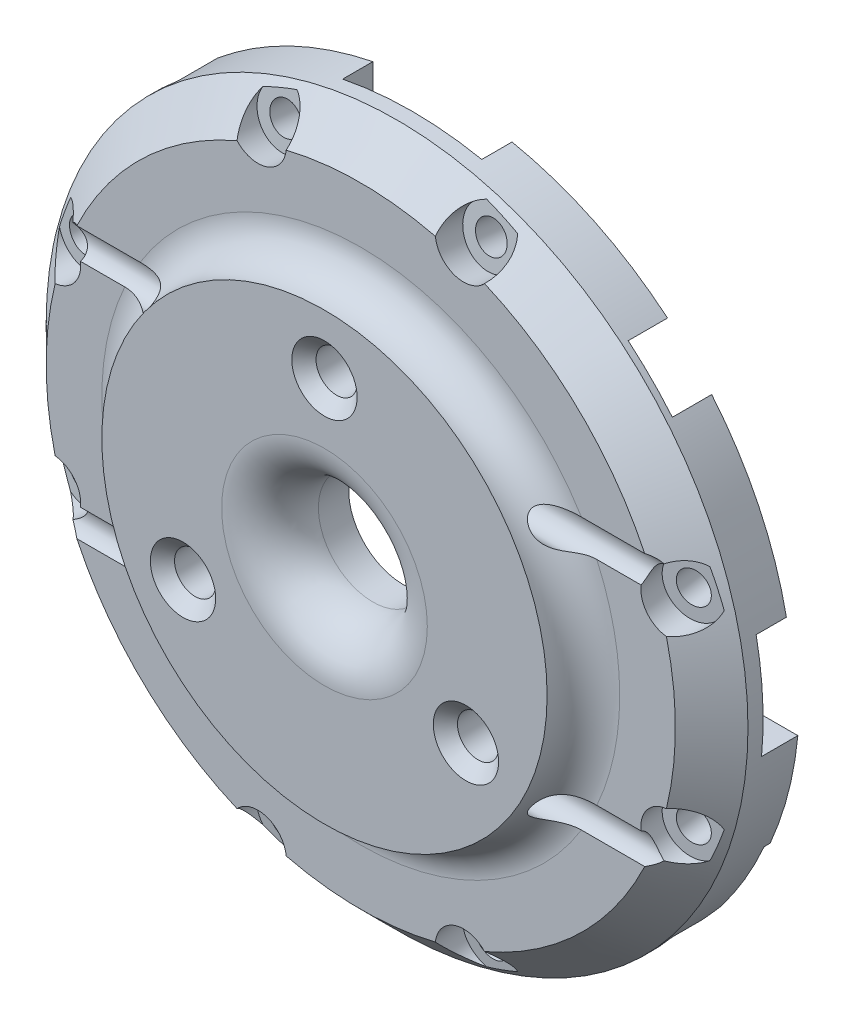
SolidWorks part; units mm, degrees
ref_plane "Front Plane" through (0, 0, 0) normal (0, 0, 1) x (1, 0, 0)
ref_plane "Top Plane" through (0, 0, 0) normal (0, 1, 0) x (1, 0, 0)
ref_plane "Right Plane" through (0, 0, 0) normal (1, 0, 0) x (0, 0, -1)
sketch "Sketch1" plane through (0, 0, 0) normal (0, 0, 1) x (1, 0, 0)
  circle A0 centre (0, 0) radius 29
  dimension "D1" = 58
extrude "Boss-Extrude1" add sketch "Sketch1" along normal blind 6.75
sketch "Sketch3" plane through (0, 0, 0) normal (0, 0, -1) x (-1, 0, 0)
  line L1 (-22.25, -22.25) -> (22.25, -22.25)
  line L2 (-22.25, -22.25) -> (-22.25, 22.25)
  line L3 (-22.25, 22.25) -> (22.25, 22.25)
  line L4 (22.25, -22.25) -> (22.25, 22.25)
  line L5 (-22.25, -22.25) -> (22.25, 22.25) construction
  line L6 (-22.25, 22.25) -> (22.25, -22.25) construction
  point P0 (0, 0)
  dimension "D1" = 44.5
extrude "Cut-Extrude1" cut sketch "Sketch3" against normal blind 3.25
sketch "Sketch4" plane through (0, 0, 6.75) normal (0, 0, 1) x (1, 0, 0)
  circle A0 centre (0, 0) radius 18.4
  dimension "D1" = 36.8
extrude "Boss-Extrude2" add sketch "Sketch4" along normal blind 3
fillet "Fillet1" radius 3 1 edges at (18.4, 0, 6.75)
sketch "Sketch5" plane through (0, 0, 9.75) normal (0, 0, 1) x (1, 0, 0)
  line L0 (-11.6913, -6.75) -> (0, 13.5) construction
  line L1 (0, 13.5) -> (11.6913, -6.75) construction
  line L2 (11.6913, -6.75) -> (-11.6913, -6.75) construction
  circle A2 centre (0, 0) radius 13.5 construction
  circle A3 centre (0, 13.5) radius 1.7
  circle A4 centre (11.6913, -6.75) radius 1.7
  circle A5 centre (-11.6913, -6.75) radius 1.7
  dimension "D1" = 3.4
  dimension "D2" = 27
extrude "Cut-Extrude2" cut sketch "Sketch5" against normal through all
sketch "Sketch7" plane through (0, 0, 3.25) normal (0, 0, -1) x (-1, 0, 0)
  circle A0 centre (-11.6913, -6.75) radius 3.25
  circle A1 centre (11.6913, -6.75) radius 3.25
  circle A2 centre (0, 13.5) radius 3.25
  dimension "D1" = 6.5
extrude "Cut-Extrude3" cut sketch "Sketch7" against normal blind 2
chamfer "Chamfer2" distance 3 angle 45 1 edges at (29, 0, 6.75)
sketch "Sketch9" plane through (0, 0, 0) normal (1, 0, 0) x (0, 0, -1)
  line L0 (-26.5723, 0) -> (15.7273, 0) construction
  line L2 (-6.75, 21.4) -> (-6.75, -21.4) construction
  circle A0 centre (-7.25, 10) radius 1.3
  circle A1 centre (-7.25, -10) radius 1.3
  dimension "D1" = 2.6
  dimension "D2" = 20
  dimension "D3" = 0.5
extrude "Cut-Extrude5" cut sketch "Sketch9" against normal through all both and the other way through all
sketch "Sketch10" plane through (0, 0, 0) normal (0, 0, -1) x (-1, 0, 0)
  line L0 (5.75, -22.0007) -> (5.75, -34.0342)
  line L1 (22.0007, 5.75) -> (34.0342, 5.75)
  line L2 (22.0007, 5.75) -> (22.0007, -5.75)
  line L3 (22.0007, -5.75) -> (34.0342, -5.75)
  line L4 (34.0342, 5.75) -> (34.0342, -5.75)
  line L5 (5.75, -22.0007) -> (-5.75, -22.0007)
  line L6 (-5.75, -22.0007) -> (-5.75, -34.0342)
  line L7 (5.75, -34.0342) -> (-5.75, -34.0342)
  line L8 (-22.0007, -5.75) -> (-34.0342, -5.75)
  line L9 (-22.0007, -5.75) -> (-22.0007, 5.75)
  line L10 (-22.0007, 5.75) -> (-34.0342, 5.75)
  line L11 (-34.0342, -5.75) -> (-34.0342, 5.75)
  line L12 (-5.75, 22.0007) -> (-5.75, 34.0342)
  line L13 (-5.75, 22.0007) -> (5.75, 22.0007)
  line L14 (5.75, 22.0007) -> (5.75, 34.0342)
  line L15 (-5.75, 34.0342) -> (5.75, 34.0342)
  point P4 (22.0007, 0)
  point P21 (0, 0)
  dimension "D1" = 11.5
  dimension "D2" = 4
extrude "Cut-Extrude6" cut sketch "Sketch10" against normal blind 2.5
sketch "Sketch13" plane through (0, 0, 3.25) normal (0, 0, -1) x (-1, 0, 0)
  line L0 (-22.25, 18.5994) -> (-22.25, -18.5994) construction
  line L1 (-22.15, 14.75) -> (-15.65, 14.75)
  line L2 (-22.15, 14.75) -> (-22.15, 8.25)
  line L3 (-22.15, 8.25) -> (-15.65, 8.25)
  line L4 (-15.65, 14.75) -> (-15.65, 8.25)
  line L5 (18.5994, 22.25) -> (-18.5994, 22.25) construction
  line L6 (14.75, 22.15) -> (14.75, 15.65)
  line L7 (14.75, 22.15) -> (8.25, 22.15)
  line L8 (8.25, 22.15) -> (8.25, 15.65)
  line L9 (14.75, 15.65) -> (8.25, 15.65)
  line L10 (22.15, -14.75) -> (15.65, -14.75)
  line L11 (22.15, -14.75) -> (22.15, -8.25)
  line L12 (22.15, -8.25) -> (15.65, -8.25)
  line L13 (15.65, -14.75) -> (15.65, -8.25)
  line L14 (-14.75, -22.15) -> (-14.75, -15.65)
  line L15 (-14.75, -22.15) -> (-8.25, -22.15)
  line L16 (-8.25, -22.15) -> (-8.25, -15.65)
  line L17 (-14.75, -15.65) -> (-8.25, -15.65)
  point P23 (0, 0)
  dimension "D1" = 0.1
  dimension "D2" = 7.5
  dimension "D4" = 6.5
  dimension "D3" = 4
extrude "Cut-Extrude9" cut sketch "Sketch13" against normal blind 2.25
chamfer "Chamfer5" distance 1 angle 45 12 edges at (-14.75, 18.9, 3.25) (-11.5, 15.65, 3.25) (-8.25, 18.9, 3.25) (14.75, -18.9, 3.25) (11.5, -15.65, 3.25) (8.25, -18.9, 3.25) (-18.9, -8.25, 3.25) (-15.65, -11.5, 3.25) (-18.9, -14.75, 3.25) (18.9, 8.25, 3.25) (15.65, 11.5, 3.25) (18.9, 14.75, 3.25)
sketch "Sketch14" plane through (0, 0, 0) normal (0, 0, -1) x (-1, 0, 0)
  line L1 (-35.1198, 0) -> (-19.2322, 0)
  line L2 (-35.1198, 0) -> (-35.1198, -11.6)
  line L3 (-35.1198, -11.6) -> (-19.2322, -11.6)
  line L4 (-19.2322, 0) -> (-19.2322, -11.6)
  dimension "D1" = 11.6
extrude "Cut-Extrude10" cut sketch "Sketch14" against normal up to surface (2.5 mm away) up to face at (25.4811, 0, 2.5)
fillet "Fillet2" radius 1.5 3 edges at (-8.5776, -5.8189, 3.25) (8.4413, -6.75, 3.25) (-3.25, 13.5, 3.25)
sketch "Sketch15" plane through (0, 0, 6.75) normal (0, 0, 1) x (1, 0, 0)
  line L0 (0, 0) -> (11.6673, 11.6673) construction
  line L1 (0, 0) -> (36.7921, 0) construction
  circle A0 centre (11.6673, 11.6673) radius 12.5
  circle A1 centre (0, 0) radius 29 construction
  dimension "D2" = 25
  dimension "D1" = 45
sketch "Sketch19" plane through (0, 0, 2.5) normal (0, 0, -1) x (-1, 0, 0)
  line L0 (-22.25, -2.75) -> (-22.25, -11.6)
  line L1 (-22.25, -11.6) -> (-22.25, 5.75) construction
  line L2 (-22.25, -11.6) -> (-26.5789, -11.6)
  line L3 (-22.25, -2.75) -> (-28.8693, -2.75)
  line L4 (-22.25, 5.75) -> (-28.4242, 5.75) construction
  arc A0 (-28.8693, -2.75) -> (-26.5789, -11.6) centre (0, 0) ccw
  arc A1 (-28.4242, 5.75) -> (-26.5789, -11.6) centre (0, 0) ccw construction
  dimension "D1" = 8.5
extrude "Boss-Extrude3" add sketch "Sketch19" along normal blind 3
chamfer "Chamfer7" distance 1.25 angle 45 1 edges at (22.25, -7.175, -0.5)
sketch "Sketch16" plane through (0, 0, 9.75) normal (0, 0, 1) x (1, 0, 0)
  circle A0 centre (0, 0) radius 4.5
  dimension "D1" = 9
extrude "Cut-Extrude11" cut sketch "Sketch16" against normal through all
fillet "Fillet3" radius 4 1 edges at (4.5, 0, 9.75)
chamfer "Chamfer6" distance 1 angle 45 3 edges at (13.3913, -6.75, 9.75) (-9.9913, -6.75, 9.75) (1.7, 13.5, 9.75)
ref_axis "Axis1" through (0, 0, -0.4875) along (0, 0, 1)
ref_axis "Axis2" through (0, 31.9, 0) along (0, -1, 0)
ref_plane "Plane1" through (0, 0, 0) normal (0.1219, 0, 0.9925) x (0, -1, 0)
sketch "Sketch17" plane through (0, 0, 0) normal (0.1219, 0, 0.9925) x (0, -1, 0)
  line L0 (0, 0) -> (0, 33.2124) construction
  line L1 (0, 0.0594) -> (0, -1.2476) construction
  circle A0 centre (-8.5, 24.5) radius 1.3
  circle A1 centre (8.5, 24.5) radius 1.3
  dimension "D1" = 2.6
  dimension "D2" = 17
  dimension "D3" = 24.5
extrude "Cut-Extrude12" cut sketch "Sketch17" along normal through all
sketch "Sketch18" plane through (0, 0, 0) normal (0.1219, 0, 0.9925) x (0, -1, 0)
  circle A0 centre (-8.5, 24.5) radius 2.35
  circle A1 centre (8.5, 24.5) radius 2.35
  dimension "D1" = 4.7
extrude "Cut-Extrude13" cut sketch "Sketch18" against normal blind 12.5 from offset 20
pattern_circular "CirPattern1" count 4 over 360 about axis through (0, 0, -0.4875) along (0, 0, 1) of "Cut-Extrude12", "Cut-Extrude13"
